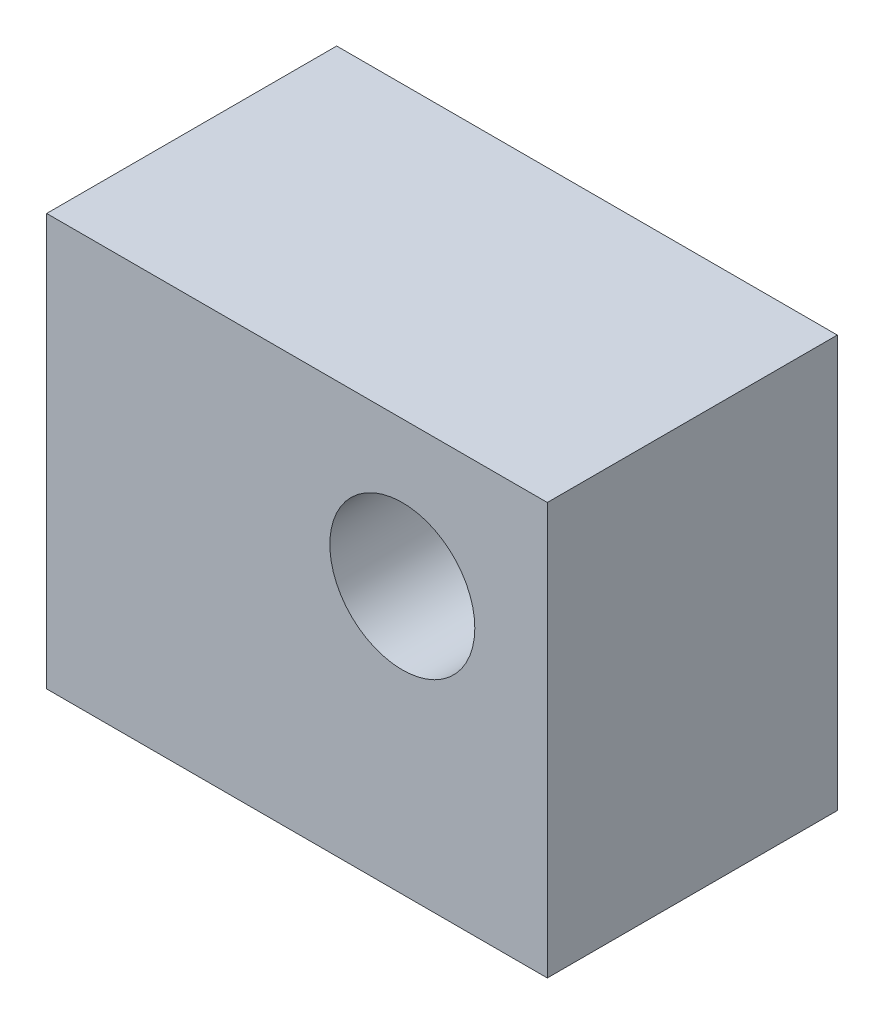
SolidWorks part; units mm, degrees
material "1060 Alloy"
ref_plane "Front" through (0, 0, 0) normal (0, 0, 1) x (1, 0, 0)
ref_plane "Top" through (0, 0, 0) normal (0, 1, 0) x (1, 0, 0)
ref_plane "Right" through (0, 0, 0) normal (1, 0, 0) x (0, 0, -1)
sketch "Sketch3" plane through (0, 0, 0) normal (0, 0, 1) x (1, 0, 0)
  line L0 (-0.127, -6.35) -> (30.1755, -6.35)
  line L1 (0, 0) -> (21.9242, 0)
  line L2 (0, 0) -> (0, -19.8376)
  line L3 (0, -19.8376) -> (21.9242, -19.8376)
  line L4 (21.9242, 0) -> (21.9242, -19.8376)
  line L5 (15.5742, -19.8376) -> (15.5742, 0) construction
  line L6 (15.5742, -6.35) -> (8.0621, -19.3614) construction
  line L15 (12.5496, -11.5887) -> (15.5742, -13.335) construction
  circle A0 centre (15.5742, -6.35) radius 6.0492 construction
  point P14 (0, -6.35)
  point P17 (9.525, -6.35)
  point P20 (7.7871, -19.8376)
  dimension "D2" = 6.35
  dimension "D6" = 3.4925
  dimension "D3" = 60
  dimension "D1" = 9.525
  dimension "D4" = 9.525
  dimension "D5" = 6.35
extrude "Boss-Extrude1" add sketch "Sketch3" along normal mid plane 12.7
sketch "Sketch4" plane through (0, 0, 0) normal (-1, 0, 0) x (0, 0, 1)
  circle A0 centre (0, -6.35) radius 3.175
  dimension "D1" = 6.35
extrude "Cut-Extrude1" cut sketch "Sketch4" against normal blind 9.525
ref_plane "Plane1" through (7.7871, -19.8376, 0) normal (-0.5, -0.866, 0) x (-0.866, 0.5, 0)
ref_plane "Mirror Plane" through (15.5742, 0, 0) normal (-1, 0, 0) x (0, 0, 1)
sketch "Sketch5" plane through (7.7871, -19.8376, 0) normal (-0.5, -0.866, 0) x (-0.866, 0.5, 0)
  circle A0 centre (0, 0) radius 3.175
  dimension "D1" = 6.35
extrude "Cut-Extrude5" cut sketch "Sketch5" against normal blind 9.525 and the other way up to next
sketch "Sketch6" plane through (0, 0, 6.35) normal (0, 0, -1) x (-1, 0, 0)
  circle A0 centre (-15.5742, -6.35) radius 3.175
  dimension "D1" = 6.35
extrude "Cut-Extrude6" cut sketch "Sketch6" along normal blind 9.525
sketch "Sketch7" plane through (21.9242, 0, 0) normal (1, 0, 0) x (0, 0, -1)
  line L0 (-6.35, -19.8376) -> (-6.35, 0) construction
  line L1 (-6.35, -18.034) -> (6.35, -18.034)
  line L2 (-6.35, -18.034) -> (-6.35, -19.8376)
  line L3 (-6.35, -19.8376) -> (6.35, -19.8376)
  line L4 (6.35, -18.034) -> (6.35, -19.8376)
  line L5 (-6.35, 0) -> (6.35, 0) construction
  dimension "D1" = 18.034
extrude "Cut-Extrude8" cut sketch "Sketch7" against normal through all
equation "\"truss_member_od\" = .25in"
equation "\"truss_member_id\"= 0in"
equation "\"truss_member_L1\" = 2.125in"
equation "\"connector_hole_depth\" = .375in"
equation "\"D1@Boss-Extrude1\"=\"truss_member_od\"*2"
equation "\"D6@Sketch3\"=\"truss_member_od\"/2*1.1"
equation "\"D1@Sketch4\"=\"truss_member_od\""
equation "\"D1@Cut-Extrude1\"=\"connector_hole_depth\""
equation "\"D1@Sketch3\"=\"connector_hole_depth\""
equation "\"D4@Sketch3\"=\"connector_hole_depth\""
equation "\"D1@Sketch5\"=\"truss_member_od\""
equation "\"D1@Cut-Extrude5\"=\"connector_hole_depth\""
equation "\"D1@Cut-Extrude6\"=\"connector_hole_depth\""
equation "\"D1@Sketch6\"=\"truss_member_od\""
equation "\"D5@Sketch3\"=\"truss_member_od\""
